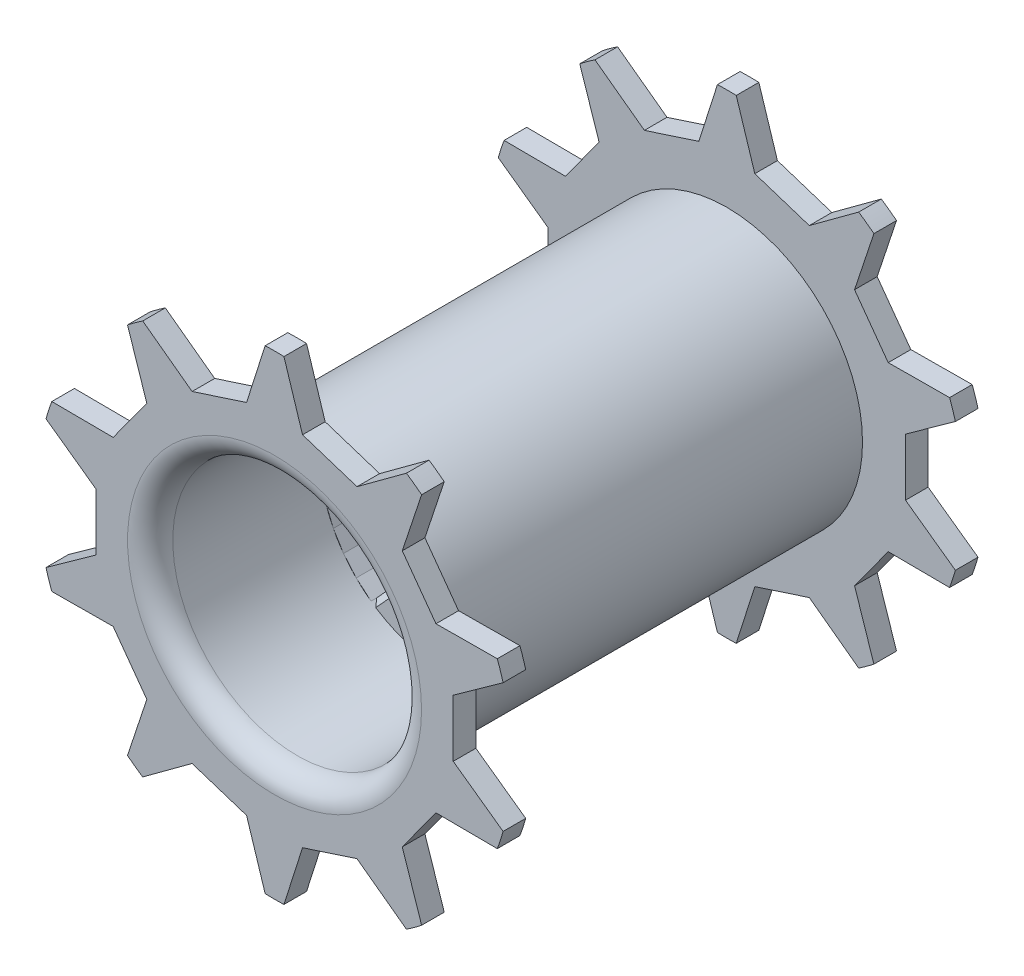
SolidWorks part; units mm, degrees
ref_plane "Front Plane" through (0, 0, 0) normal (0, 0, 1) x (1, 0, 0)
ref_plane "Top Plane" through (0, 0, 0) normal (0, 1, 0) x (1, 0, 0)
ref_plane "Right Plane" through (0, 0, 0) normal (1, 0, 0) x (0, 0, -1)
sketch "Sketch1" plane through (0, 0, 0) normal (0, 0, 1) x (1, 0, 0)
  circle A0 centre (0, 0) radius 21
extrude "Boss-Extrude1" add sketch "Sketch1" along normal blind 2
sketch "Sketch4" plane through (0, 0, 0) normal (0, 0, -1) x (-1, 0, 0)
  circle A0 centre (0, 0) radius 12
extrude "Boss-Extrude2" add sketch "Sketch4" along normal blind 38
sketch "Sketch5" plane through (0, 0, -38) normal (0, 0, -1) x (-1, 0, 0)
  circle A0 centre (0, 0) radius 21
extrude "Boss-Extrude3" add sketch "Sketch5" along normal blind 2
sketch "Sketch6" plane through (0, 0, 2) normal (0, 0, 1) x (1, 0, 0)
  line L0 (-2.503, 15.803) -> (-1.6476, 20.9353)
  line L2 (7.2638, 14.2561) -> (2.503, 15.803)
  line L4 (-2.503, 15.803) -> (-7.2638, 14.2561)
  line L6 (-11.3137, 11.3137) -> (-14.2561, 7.2638)
  line L8 (-15.803, 2.503) -> (-15.803, -2.503)
  line L10 (-14.2561, -7.2638) -> (-11.3137, -11.3137)
  line L12 (-7.2638, -14.2561) -> (-2.503, -15.803)
  line L14 (2.503, -15.803) -> (7.2638, -14.2561)
  line L16 (11.3137, -11.3137) -> (14.2561, -7.2638)
  line L18 (15.803, -2.503) -> (15.803, 2.503)
  line L20 (14.2561, 7.2638) -> (11.3137, 11.3137)
  line L61 (1.6476, 20.9353) -> (2.503, 15.803)
  line L62 (7.2638, 14.2561) -> (10.9725, 17.9054)
  line L63 (13.6384, 15.9685) -> (11.3137, 11.3137)
  line L64 (-7.2638, 14.2561) -> (-10.9725, 17.9054)
  line L65 (-13.6384, 15.9685) -> (-11.3137, 11.3137)
  line L66 (-14.2561, 7.2638) -> (-19.4015, 8.0364)
  line L67 (-20.4198, 4.9024) -> (-15.803, 2.503)
  line L68 (-15.803, -2.503) -> (-20.4198, -4.9024)
  line L69 (-19.4015, -8.0364) -> (-14.2561, -7.2638)
  line L70 (-11.3137, -11.3137) -> (-13.6384, -15.9685)
  line L71 (-7.2638, -14.2561) -> (-10.9725, -17.9054)
  line L72 (-2.503, -15.803) -> (-1.6476, -20.9353)
  line L73 (2.503, -15.803) -> (1.6476, -20.9353)
  line L74 (7.2638, -14.2561) -> (10.9725, -17.9054)
  line L75 (11.3137, -11.3137) -> (13.6384, -15.9685)
  line L76 (14.2561, -7.2638) -> (19.4015, -8.0364)
  line L77 (20.4198, -4.9024) -> (15.803, -2.503)
  line L78 (15.803, 2.503) -> (20.4198, 4.9024)
  line L79 (14.2561, 7.2638) -> (19.4015, 8.0364)
  line L80 (2.503, 15.803) -> (-2.503, 15.803) [skipped]
  line L81 (-7.2638, 14.2561) -> (-11.3137, 11.3137) [skipped]
  line L82 (-14.2561, 7.2638) -> (-15.803, 2.503) [skipped]
  line L83 (-15.803, -2.503) -> (-14.2561, -7.2638) [skipped]
  line L84 (-11.3137, -11.3137) -> (-7.2638, -14.2561) [skipped]
  line L85 (-2.503, -15.803) -> (2.503, -15.803) [skipped]
  line L86 (7.2638, -14.2561) -> (11.3137, -11.3137) [skipped]
  line L87 (14.2561, -7.2638) -> (15.803, -2.503) [skipped]
  line L88 (15.803, 2.503) -> (14.2561, 7.2638) [skipped]
  line L89 (11.3137, 11.3137) -> (7.2638, 14.2561) [skipped]
  line L90 (-10.9725, 17.9054) -> (-15.3997, 21.4083)
  line L91 (-15.3997, 21.4083) -> (-1.0976, 25.4459)
  line L92 (-1.0976, 25.4459) -> (-1.6476, 20.9353)
  line L93 (1.6476, 20.9353) -> (1.6476, 28.3087)
  line L94 (1.6476, 28.3087) -> (14.7199, 24.622)
  line L95 (14.7199, 24.622) -> (10.9725, 17.9054)
  line L96 (13.6384, 15.9685) -> (17.7967, 22.3302)
  line L97 (17.7967, 22.3302) -> (26.0957, 10.5583)
  line L98 (26.0957, 10.5583) -> (19.4015, 8.0364)
  line L99 (20.4198, 4.9024) -> (29.723, 9.2973)
  line L100 (29.723, 9.2973) -> (28.5835, -9.1173)
  line L101 (28.5835, -9.1173) -> (20.4198, -4.9024)
  line L102 (19.4015, -8.0364) -> (25.4256, -9.6511)
  line L103 (25.4256, -9.6511) -> (18.8058, -21.5159)
  line L104 (18.8058, -21.5159) -> (13.6384, -15.9685)
  line L105 (1.6476, -20.9353) -> (0.6806, -30.1006)
  line L106 (0.6806, -30.1006) -> (15.803, -25.187)
  line L107 (15.803, -25.187) -> (10.9725, -17.9054)
  line L108 (-1.6476, -20.9353) -> (3.8143, -30.1006)
  line L109 (3.8143, -30.1006) -> (-17.0342, -25.5179)
  line L110 (-17.0342, -25.5179) -> (-10.9725, -17.9054)
  line L111 (-13.6384, -15.9685) -> (-18.4357, -27.1418)
  line L112 (-18.4357, -27.1418) -> (-26.3374, -9.1173)
  line L113 (-26.3374, -9.1173) -> (-19.4015, -8.0364)
  line L114 (-20.4198, -4.9024) -> (-27.0706, -11.6612)
  line L115 (-27.0706, -11.6612) -> (-27.0706, 8.0364)
  line L116 (-27.0706, 8.0364) -> (-20.4198, 4.9024)
  line L117 (-19.4015, 8.0364) -> (-28.7828, 6.5743)
  line L118 (-28.7828, 6.5743) -> (-15.2072, 23.6229)
  line L119 (-15.2072, 23.6229) -> (-13.6384, 15.9685)
  circle M2 centre (0, 0) radius 21
extrude "Cut-Extrude1" cut sketch "Sketch6" against normal blind 97 contours L66 L6 L65 M2 | L64 L4 L0 M2 | L2 L62 L61 M2 | L20 L79 L63 M2 | L78 L18 L77 M2 | L76 L16 L75 M2 | L74 L14 L73 M2 | L72 L12 L71 M2 | L70 L10 L69 M2 | L68 L8 L67 M2 region at (-5.7447, 17.6802, 2) region at (5.7447, 17.6802, 2) region at (-15.0397, 10.927, 2) region at (15.0397, 10.927, 2) region at (-18.5901, 0, 2) region at (18.5901, 0, 2) region at (-15.0397, -10.927, 2) region at (15.0397, -10.927, 2) region at (-5.7447, -17.6802, 2) region at (5.7447, -17.6802, 2)
sketch "Sketch7" plane through (0, 0, -40) normal (0, 0, -1) x (-1, 0, 0)
  circle A0 centre (0, 0) radius 11
extrude "Cut-Extrude3" cut sketch "Sketch7" against normal blind 15 contours A0
sketch "Sketch9" plane through (0, 0, 2) normal (0, 0, 1) x (1, 0, 0)
  circle A0 centre (0, 0) radius 11
extrude "Cut-Extrude4" cut sketch "Sketch9" against normal blind 15
sketch "Sketch10" plane through (0, 0, -13) normal (0, 0, 1) x (1, 0, 0)
  circle A0 centre (0, 0) radius 3.05
extrude "Cut-Extrude5" cut sketch "Sketch10" against normal through all both and the other way through all
sketch "Sketch11" plane through (0, 0, -25) normal (0, 0, -1) x (-1, 0, 0)
  line L0 (-0.7223, 4.5603) -> (0, 11)
  line L41 (0, 11) -> (-1.7208, 10.8646)
  line L42 (-1.7208, 10.8646) -> (-3.3992, 10.4616)
  line L43 (-3.3992, 10.4616) -> (-4.9939, 9.8011)
  line L44 (-4.9939, 9.8011) -> (-6.4656, 8.8992)
  line L45 (-6.4656, 8.8992) -> (-7.7782, 7.7782)
  line L46 (-7.7782, 7.7782) -> (-8.8992, 6.4656)
  line L47 (-8.8992, 6.4656) -> (-9.8011, 4.9939)
  line L48 (-9.8011, 4.9939) -> (-10.4616, 3.3992)
  line L49 (-10.4616, 3.3992) -> (-10.8646, 1.7208)
  line L50 (-10.8646, 1.7208) -> (-11, 0)
  line L51 (-11, 0) -> (-10.8646, -1.7208)
  line L52 (-10.8646, -1.7208) -> (-10.4616, -3.3992)
  line L53 (-10.4616, -3.3992) -> (-9.8011, -4.9939)
  line L54 (-9.8011, -4.9939) -> (-8.8992, -6.4656)
  line L55 (-8.8992, -6.4656) -> (-7.7782, -7.7782)
  line L56 (-7.7782, -7.7782) -> (-6.4656, -8.8992)
  line L57 (-6.4656, -8.8992) -> (-4.9939, -9.8011)
  line L58 (-4.9939, -9.8011) -> (-3.3992, -10.4616)
  line L59 (-3.3992, -10.4616) -> (-1.7208, -10.8646)
  line L60 (-1.7208, -10.8646) -> (0, -11)
  line L61 (0, -11) -> (1.7208, -10.8646)
  line L62 (1.7208, -10.8646) -> (3.3992, -10.4616)
  line L63 (3.3992, -10.4616) -> (4.9939, -9.8011)
  line L64 (4.9939, -9.8011) -> (6.4656, -8.8992)
  line L65 (6.4656, -8.8992) -> (7.7782, -7.7782)
  line L66 (7.7782, -7.7782) -> (8.8992, -6.4656)
  line L67 (8.8992, -6.4656) -> (9.8011, -4.9939)
  line L68 (9.8011, -4.9939) -> (10.4616, -3.3992)
  line L69 (10.4616, -3.3992) -> (10.8646, -1.7208)
  line L70 (10.8646, -1.7208) -> (11, 0)
  line L71 (11, 0) -> (10.8646, 1.7208)
  line L72 (10.8646, 1.7208) -> (10.4616, 3.3992)
  line L73 (10.4616, 3.3992) -> (9.8011, 4.9939)
  line L74 (9.8011, 4.9939) -> (8.8992, 6.4656)
  line L75 (8.8992, 6.4656) -> (7.7782, 7.7782)
  line L76 (7.7782, 7.7782) -> (6.4656, 8.8992)
  line L77 (6.4656, 8.8992) -> (4.9939, 9.8011)
  line L78 (4.9939, 9.8011) -> (3.3992, 10.4616)
  line L79 (3.3992, 10.4616) -> (1.7208, 10.8646)
  line L80 (1.7208, 10.8646) -> (0, 11)
  line L81 (-3.2648, -3.2648) -> (-2.0961, -4.1139)
  line L82 (-2.0961, -4.1139) -> (-0.7223, -4.5603)
  line L83 (-0.7223, -4.5603) -> (0.7223, -4.5603)
  line L84 (0.7223, -4.5603) -> (2.0961, -4.1139)
  line L85 (2.0961, -4.1139) -> (3.2648, -3.2648)
  line L86 (3.2648, -3.2648) -> (4.1139, -2.0961)
  line L87 (4.1139, -2.0961) -> (4.5603, -0.7223)
  line L88 (4.5603, -0.7223) -> (4.5603, 0.7223)
  line L89 (4.5603, 0.7223) -> (4.1139, 2.0961)
  line L90 (4.1139, 2.0961) -> (3.2648, 3.2648)
  line L91 (3.2648, 3.2648) -> (2.0961, 4.1139)
  line L92 (2.0961, 4.1139) -> (0.7223, 4.5603)
  line L93 (0.7223, 4.5603) -> (-0.7223, 4.5603)
  line L94 (-0.7223, 4.5603) -> (-2.0961, 4.1139)
  line L95 (-2.0961, 4.1139) -> (-3.2648, 3.2648)
  line L96 (-3.2648, 3.2648) -> (-4.1139, 2.0961)
  line L97 (-4.1139, 2.0961) -> (-4.5603, 0.7223)
  line L98 (-4.5603, 0.7223) -> (-4.5603, -0.7223)
  line L99 (-4.5603, -0.7223) -> (-4.1139, -2.0961)
  line L100 (-4.1139, -2.0961) -> (-3.2648, -3.2648)
  line L101 (0.7223, 4.5603) -> (0, 11)
  line L102 (2.0961, 4.1139) -> (3.3992, 10.4616)
  line L103 (0.7223, 4.5603) -> (3.3992, 10.4616)
  line L104 (2.0961, 4.1139) -> (6.4656, 8.8992)
  line L105 (3.2648, 3.2648) -> (6.4656, 8.8992)
  line L106 (3.2648, 3.2648) -> (8.8992, 6.4656)
  line L107 (8.8992, 6.4656) -> (4.1139, 2.0961)
  line L108 (4.1139, 2.0961) -> (10.4616, 3.3992)
  line L109 (4.5603, 0.7223) -> (10.4616, 3.3992)
  line L110 (4.5603, 0.7223) -> (11, 0)
  line L111 (4.5603, -0.7223) -> (11, 0)
  line L112 (4.5603, -0.7223) -> (10.4616, -3.3992)
  line L113 (4.1139, -2.0961) -> (10.4616, -3.3992)
  line L114 (4.1139, -2.0961) -> (8.8992, -6.4656)
  line L115 (3.2648, -3.2648) -> (8.8992, -6.4656)
  line L116 (2.0961, -4.1139) -> (6.4656, -8.8992)
  line L117 (3.2648, -3.2648) -> (6.4656, -8.8992)
  line L118 (2.0961, -4.1139) -> (3.3992, -10.4616)
  line L119 (0.7223, -4.5603) -> (3.3992, -10.4616)
  line L120 (-0.7223, -4.5603) -> (0, -11)
  line L121 (0.7223, -4.5603) -> (0, -11)
  line L122 (-0.7223, -4.5603) -> (-3.3992, -10.4616)
  line L123 (-2.0961, -4.1139) -> (-3.4949, -10.422)
  line L124 (-2.0961, -4.1139) -> (-6.4656, -8.8992)
  line L125 (-3.2648, -3.2648) -> (-6.4656, -8.8992)
  line L126 (-3.2648, -3.2648) -> (-8.8992, -6.4656)
  line L127 (-4.1139, -2.0961) -> (-8.8992, -6.4656)
  line L128 (-4.1139, -2.0961) -> (-10.4616, -3.3992)
  line L129 (-4.5603, -0.7223) -> (-10.4616, -3.3992)
  line L130 (-4.5603, -0.7223) -> (-11, 0)
  line L131 (-11, 0) -> (-4.5603, 0.7223)
  line L132 (-10.4616, 3.3992) -> (-4.5603, 0.7223)
  line L133 (-10.4616, 3.3992) -> (-4.1139, 2.0961)
  line L134 (-4.1139, 2.0961) -> (-8.8992, 6.4656)
  line L135 (-8.8992, 6.4656) -> (-3.2648, 3.2648)
  line L136 (-3.2648, 3.2648) -> (-6.4656, 8.8992)
  line L137 (-2.0961, 4.1139) -> (-6.4656, 8.8992)
  line L138 (-2.0961, 4.1139) -> (-3.3992, 10.4616)
  line L139 (-0.7223, 4.5603) -> (-3.3992, 10.4616)
  circle A0 centre (0, 0) radius 10.9661 construction
  circle A1 centre (0, 0) radius 4.6171
  circle A2 centre (0, 0) radius 4.5603 construction
extrude "Cut-Extrude8" cut sketch "Sketch11" against normal mid plane 75 contours L137 L138 L43 L44 | L139 L0 L41 L42 | A1 L101 L0 | A1 L139 L138 | A1 L137 L136 | L132 L49 L50 L131 | A1 L131 L130 | L129 L130 L51 L52 | A1 L129 L128 | A1 L133 L132 | A1 L125 L124 | L123 L124 L57 L58 | A1 L123 L58 L122 | L120 L122 L59 L60 | A1 L120 L121 | L115 L117 L65 L66 | A1 L116 L117 | A1 L115 L114 | L113 L114 L67 L68 | A1 L113 L112 | A1 L105 L104 | L105 L106 L75 L76 | A1 L107 L106 | L107 L108 L73 L74 | A1 L109 L108 region at (1.3809, 8.7185, -25) region at (2.0804, 6.4027, -25) region at (0, 6.7322, -25) region at (3.9571, 5.4464, -25) region at (4.0075, 7.8651, -25) region at (-3.9571, 5.4464, -25) region at (-6.2418, 6.2418, -25) region at (-5.4464, 3.9571, -25) region at (6.4027, 2.0804, -25) region at (-7.8651, 4.0075, -25) region at (-6.4027, 2.0804, -25) region at (6.7322, 0, -25) region at (8.7185, 1.3809, -25) region at (6.4027, -2.0804, -25) region at (8.7185, -1.3809, -25) region at (-6.4027, -2.0804, -25) region at (-7.8651, -4.0075, -25) region at (-5.4464, -3.9571, -25) region at (3.9571, -5.4464, -25) region at (-6.2418, -6.2418, -25) region at (-3.9571, -5.4464, -25) region at (2.1416, -6.5317, -25) region at (4.0387, -7.8507, -25) region at (0, -6.7322, -25) region at (1.3809, -8.7185, -25)
chamfer "Chamfer1" distance 0.5 angle 45 20 edges at (-4.2809, -6.5065, -13) (-0.3611, -7.7801, -13) (4.8652, -6.082, -13) (7.2877, -2.7477, -13) (7.2877, 2.7477, -13) (4.8652, 6.082, -13) (-0.3611, 7.7801, -13) (-4.2809, 6.5065, -13) (-7.5109, -2.0607, -25) (-7.5109, 2.0607, -13) (4.8652, 6.082, -25) (7.2877, 2.7477, -25) (7.2877, -2.7477, -25) (4.8652, -6.082, -25) (-0.3611, -7.7801, -25) (-4.2809, -6.5065, -25) (-7.5109, -2.0607, -13) (-7.5109, 2.0607, -25) (-4.2809, 6.5065, -25) (-0.3611, 7.7801, -25)
chamfer "Chamfer3" distance 0.6 angle 70 20 edges at (-1.6476, 20.9353, -39) (-13.6384, 15.9685, -39) (-20.4198, 4.9024, -39) (-19.4015, -8.0364, -39) (-10.9725, -17.9054, -39) (1.6476, -20.9353, -39) (13.6384, -15.9685, -39) (20.4198, -4.9024, -39) (19.4015, 8.0364, -39) (10.9725, 17.9054, -39) (10.9725, 17.9054, 1) (19.4015, 8.0364, 1) (20.4198, -4.9024, 1) (13.6384, -15.9685, 1) (1.6476, -20.9353, 1) (-10.9725, -17.9054, 1) (-19.4015, -8.0364, 1) (-20.4198, 4.9024, 1) (-13.6384, 15.9685, 1) (-1.6476, 20.9353, 1) first distance on face at (0, 20.9676, -39) first distance on face at (-12.3245, 16.9632, -39) first distance on face at (-19.9414, 6.4794, -39) first distance on face at (-19.9414, -6.4794, -39) first distance on face at (-12.3245, -16.9632, -39) first distance on face at (0, -20.9676, -39) first distance on face at (12.3245, -16.9632, -39) first distance on face at (19.9414, -6.4794, -39) first distance on face at (19.9414, 6.4794, -39) first distance on face at (12.3245, 16.9632, -39) first distance on face at (12.3245, 16.9632, 1) first distance on face at (19.9414, 6.4794, 1) first distance on face at (19.9414, -6.4794, 1) first distance on face at (12.3245, -16.9632, 1) first distance on face at (0, -20.9676, 1) first distance on face at (-12.3245, -16.9632, 1) first distance on face at (-19.9414, -6.4794, 1) first distance on face at (-19.9414, 6.4794, 1) first distance on face at (-12.3245, 16.9632, 1) first distance on face at (0, 20.9676, 1)
chamfer "Chamfer4" distance 0.6 angle 70 20 edges at (19.4015, -8.0364, -39) (10.9725, -17.9054, -39) (-1.6476, -20.9353, -39) (-13.6384, -15.9685, -39) (-20.4198, -4.9024, -39) (-19.4015, 8.0364, -39) (-10.9725, 17.9054, -39) (1.6476, 20.9353, -39) (13.6384, 15.9685, -39) (20.4198, 4.9024, -39) (13.6384, 15.9685, 1) (20.4198, 4.9024, 1) (19.4015, -8.0364, 1) (10.9725, -17.9054, 1) (-1.6476, -20.9353, 1) (-13.6384, -15.9685, 1) (-20.4198, -4.9024, 1) (-19.4015, 8.0364, 1) (-10.9725, 17.9054, 1) (1.6476, 20.9353, 1) first distance on face at (19.8247, -6.8712, -39) first distance on face at (11.9997, -17.2116, -39) first distance on face at (-0.4088, -20.9777, -39) first distance on face at (-12.6611, -16.7311, -39) first distance on face at (-20.0773, -6.0937, -39) first distance on face at (-19.8247, 6.8712, -39) first distance on face at (-11.9997, 17.2116, -39) first distance on face at (0.4088, 20.9777, -39) first distance on face at (12.6611, 16.7311, -39) first distance on face at (20.0773, 6.0937, -39) first distance on face at (12.6611, 16.7311, 1) first distance on face at (20.0773, 6.0937, 1) first distance on face at (19.8247, -6.8712, 1) first distance on face at (11.9997, -17.2116, 1) first distance on face at (-0.4088, -20.9777, 1) first distance on face at (-12.6611, -16.7311, 1) first distance on face at (-20.0773, -6.0937, 1) first distance on face at (-19.8247, 6.8712, 1) first distance on face at (-11.9997, 17.2116, 1) first distance on face at (0.4088, 20.9777, 1)
sketch "Sketch12" plane through (0, 0, -25) normal (0, 0, -1) x (-1, 0, 0)
  circle A0 centre (0, 0) radius 3.05
  circle A1 centre (0, 0) radius 4.6171
  dimension "D1" = 6.1
extrude "Boss-Extrude4" add sketch "Sketch12" along normal blind 17
fillet "Fillet3" radius 1 1 edges at (-4.6171, 0, -42)
fillet "Fillet6" radius 1 1 edges at (3.05, 0, -13)
fillet "Fillet7" radius 2 1 edges at (11, 0, 2)
fillet "Fillet8" radius 2 1 edges at (-11, 0, -40)
